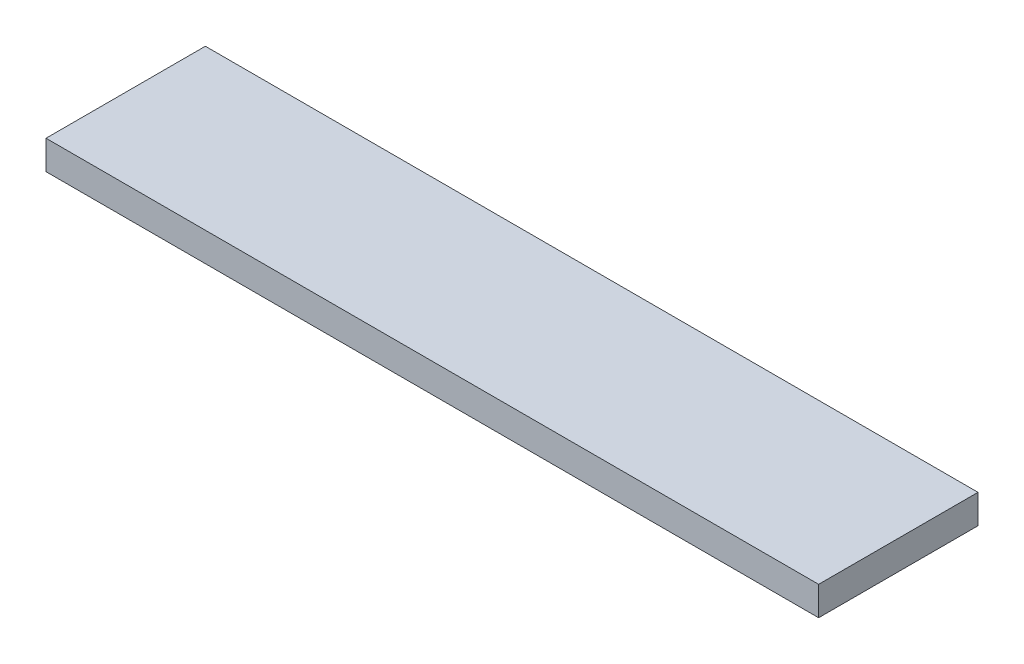
SolidWorks part; units mm, degrees
ref_plane "Front Plane" through (0, 0, 0) normal (0, 0, 1) x (1, 0, 0)
ref_plane "Top Plane" through (0, 0, 0) normal (0, 1, 0) x (1, 0, 0)
ref_plane "Right Plane" through (0, 0, 0) normal (1, 0, 0) x (0, 0, -1)
sketch "Sketch1" plane through (0, 0, 0) normal (0, 1, 0) x (1, 0, 0)
  line L1 (0, 0) -> (80, 0)
  line L2 (0, 0) -> (0, -16.5)
  line L3 (0, -16.5) -> (80, -16.5)
  line L4 (80, 0) -> (80, -16.5)
sketch "Sketch2" plane through (0, 0, 0) normal (1, 0, 0) x (0, 0, -1)
  line L1 (0, 0) -> (-16.5, 0)
  line L2 (0, 0) -> (0, -3)
  line L3 (0, -3) -> (-16.5, -3)
  line L4 (-16.5, 0) -> (-16.5, -3)
extrude "Boss-Extrude1" add sketch "Sketch1" against normal up to vertex (3 mm away) up to point (0, -3, 0)
